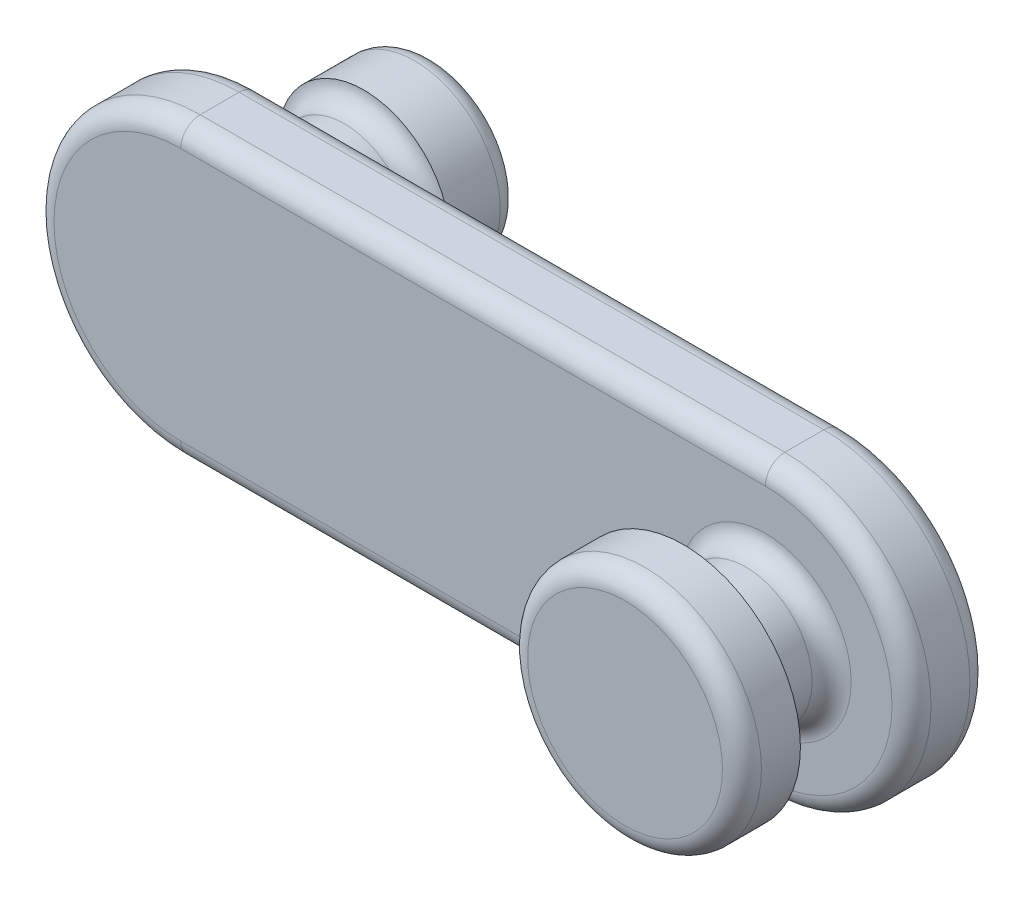
SolidWorks part; units mm, degrees
ref_plane "Front Plane" through (0, 0, 0) normal (0, 0, 1) x (1, 0, 0)
ref_plane "Top Plane" through (0, 0, 0) normal (0, 1, 0) x (1, 0, 0)
ref_plane "Right Plane" through (0, 0, 0) normal (1, 0, 0) x (0, 0, -1)
sketch "Sketch1" plane through (0, 0, 0) normal (0, 0, 1) x (1, 0, 0)
  line L0 (-15, 0) -> (15, 0) construction
  line L1 (-15, 7.5) -> (15, 7.5)
  line L2 (-15, -7.5) -> (15, -7.5)
  arc A0 (-15, 7.5) -> (-15, -7.5) centre (-15, 0) ccw
  arc A1 (15, -7.5) -> (15, 7.5) centre (15, 0) ccw
  circle A2 centre (15, 0) radius 3.5
  point P2 (0, 0)
  dimension "D3" = 7
  dimension "D1" = 15
  dimension "D2" = 30
extrude "Boss-Extrude2" add sketch "Sketch1" along normal blind 4
sketch "Sketch2" plane through (0, 0, 0) normal (0, 0, -1) x (-1, 0, 0)
  circle A0 centre (15, 0) radius 3.4
  dimension "D1" = 6.8
extrude "Boss-Extrude3" add sketch "Sketch2" along normal blind 5.4
sketch "Sketch4" plane through (0, 0, -5.4) normal (0, 0, -1) x (-1, 0, 0)
  circle A0 centre (15, 0) radius 4.4
  dimension "D1" = 8.8
extrude "Boss-Extrude4" add sketch "Sketch4" along normal blind 3.6
sketch "Sketch5" plane through (0, 0, 0) normal (0, 0, -1) x (-1, 0, 0)
  circle A0 centre (-15, 0) radius 3.5 construction
  circle A1 centre (-15, 0) radius 3.5
extrude "Boss-Extrude5" add sketch "Sketch5" against normal up to surface (4 mm away) up to face at (0, 0, 4)
sketch "Sketch6" plane through (0, 0, 4) normal (0, 0, 1) x (1, 0, 0)
  circle A0 centre (15, 0) radius 3.4
  dimension "D1" = 6.8
extrude "Boss-Extrude6" add sketch "Sketch6" along normal blind 4.2
sketch "Sketch7" plane through (0, 0, 8.2) normal (0, 0, 1) x (1, 0, 0)
  circle A0 centre (15, 0) radius 6
  dimension "D1" = 12
extrude "Boss-Extrude7" add sketch "Sketch7" along normal blind 3
fillet "Fillet1" radius 1 14 edges at (18.4, 0, 8.2) (-18.4, 0, -5.4) (22.5, 0, 4) (0, -7.5, 4) (-22.5, 0, 4) (22.5, 0, 0) (0, -7.5, 0) (-22.5, 0, 0) (21, 0, 11.2) (18.4, 0, 4) (-19.4, 0, -9) (0, 7.5, 4) (0, 7.5, 0) (-11.6, 0, 0)
